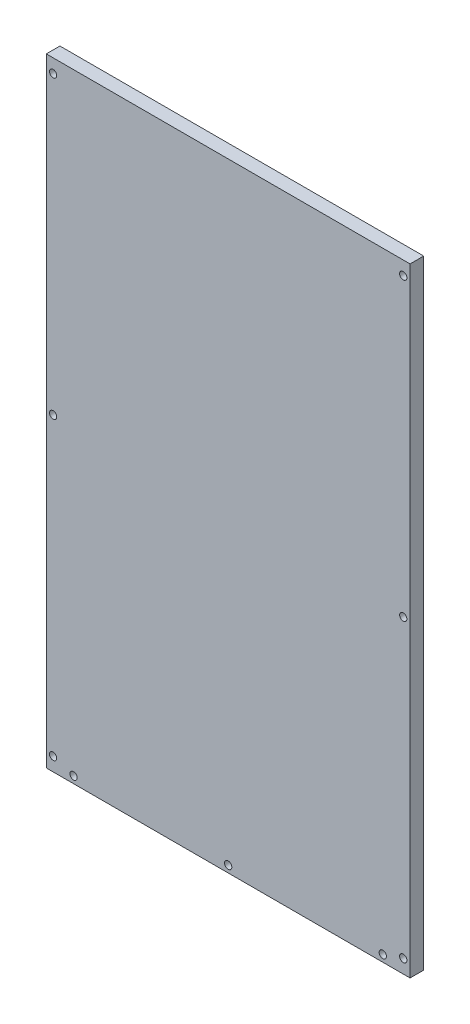
SolidWorks part; units mm, degrees
material "Oak"
ref_plane "Front Plane" through (0, 0, 0) normal (0, 0, 1) x (1, 0, 0)
ref_plane "Top Plane" through (0, 0, 0) normal (0, 1, 0) x (1, 0, 0)
ref_plane "Right Plane" through (0, 0, 0) normal (1, 0, 0) x (0, 0, -1)
sketch "Sketch1" plane through (0, 0, 0) normal (0, 0, 1) x (1, 0, 0)
  line L1 (-200, -340) -> (200, -340)
  line L2 (-200, -340) -> (-200, 340)
  line L3 (-200, 340) -> (200, 340)
  line L4 (200, -340) -> (200, 340)
  line L5 (-200, -340) -> (200, 340) construction
  line L6 (-200, 340) -> (200, -340) construction
  point P0 (0, 0)
  dimension "D1" = 400
  dimension "D2" = 680
extrude "Boss-Extrude1" add sketch "Sketch1" along normal blind 15
sketch "Sketch2" plane through (0, 0, 15) normal (0, 0, 1) x (1, 0, 0)
  line L3 (-200, -325) -> (-185, -325) construction
  line L4 (-200, 340) -> (-200, -340) construction
  line L5 (-200, -340) -> (200, -340) construction
  line L6 (185, -325) -> (185, 340)
  line L7 (-185, -325) -> (185, -325)
  line L8 (-185, 340) -> (-185, -325)
  line L9 (185, -325) -> (185, 340) construction
  line L10 (-185, -325) -> (185, -325) construction
  line L11 (-185, 340) -> (-185, -325) construction
  line L12 (-185, -325) -> (-185, -340) construction
  line L13 (200, -340) -> (200, -325) construction
  line L14 (200, -340) -> (200, 340) construction
  line L15 (-185, 340) -> (-200, 340) construction
  line L16 (-192.5, 340) -> (-192.5, 329) construction
  line L17 (0, -8.25) -> (0, 8.25) construction
  line L18 (185, -325) -> (185, -340) construction
  line L19 (200, -325) -> (185, -325) construction
  line L20 (-170, -325) -> (-170, -340) construction
  line L21 (185, -332.5) -> (174, -332.5) construction
  circle A0 centre (-192.5, 325) radius 4
  circle A1 centre (192.5, 325) radius 4
  circle A3 centre (170, -332.5) radius 4
  dimension "D1" = 15
  dimension "D4" = 8
  dimension "D6" = 8
  dimension "D2" = 15
  dimension "D5" = 11
  dimension "D8" = 15
  dimension "D3" = 15
  dimension "D7" = 11
extrude "Cut-Extrude1" cut sketch "Sketch2" against normal blind 10 contours A1 region at (192.5, 325, 15)
pattern_linear "LPattern1" count 3 spacing 325 along (0, -1, 0) of "Cut-Extrude1"
mirror "Mirror1" about plane through (0, 0, 0) normal (1, 0, 0) of "LPattern1", "Cut-Extrude1"
extrude "Cut-Extrude2" cut sketch "Sketch2<3>" against normal blind 10 contours A3 region at (170, -332.5, 15)
sketch "Sketch2<3>" plane through (0, 0, 15) normal (0, 0, 1) x (1, 0, 0) same geometry as "Sketch2"
pattern_linear "LPattern2" count 3 spacing 170 along (-1, 0, 0) of "Cut-Extrude2"
equation "\"A\"= 400mm"
equation "\"B\"= 700mm - 20mm"
equation "\"D1@Sketch1\"=\"A\""
equation "\"D2@Sketch1\"=\"B\""
equation "\"C\"= 15mm"
equation "\"D1@Boss-Extrude1\"=\"C\""
equation "\"D1@Sketch2\"=\"C\""
equation "\"`5\"=16"
